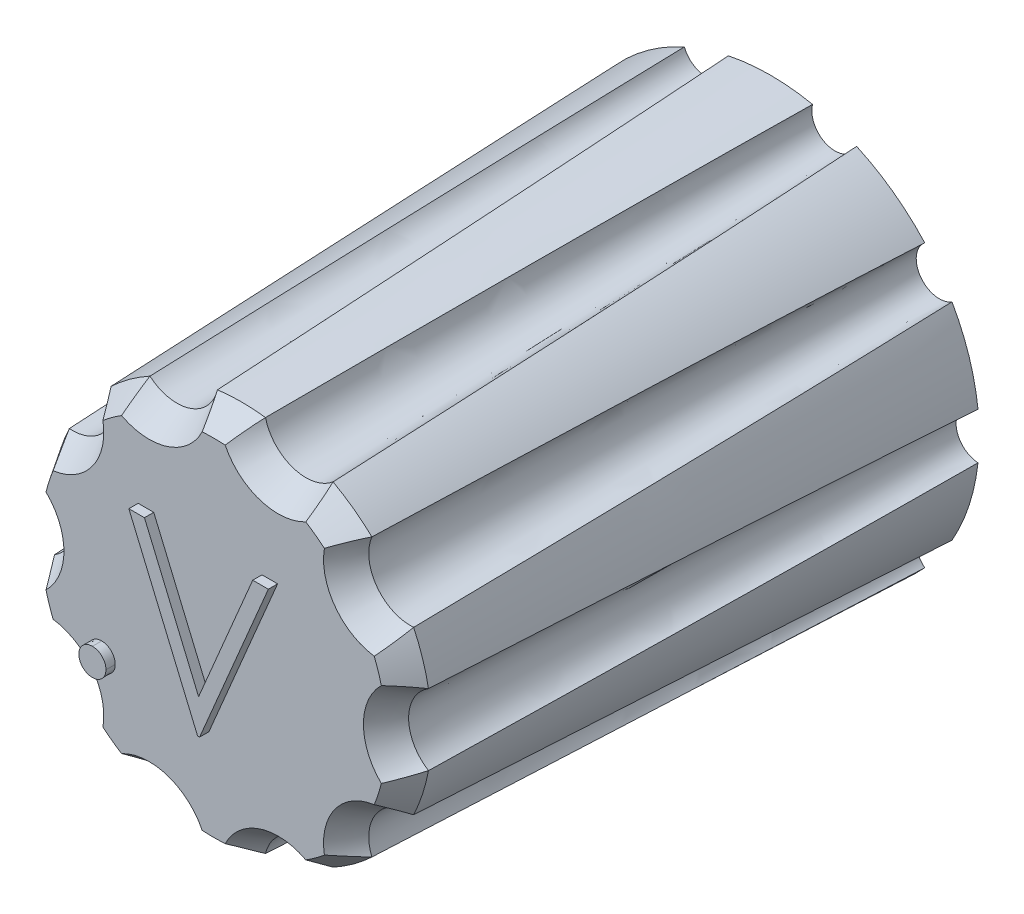
SolidWorks part; units mm, degrees
note: The reader was unsure of these and kept them because the rebuilt part matched: shared geometry of "Esquisse5<2>".
ref_plane "Plan de face" through (0, 0, 0) normal (0, 0, 1) x (1, 0, 0)
ref_plane "Plan de dessus" through (0, 0, 0) normal (0, 1, 0) x (1, 0, 0)
ref_plane "Plan de droite" through (0, 0, 0) normal (1, 0, 0) x (0, 0, -1)
sketch "Esquisse1" plane through (0, 0, 0) normal (0, 0, 1) x (1, 0, 0)
  line L0 (-13.0824, 0) -> (17.5938, 0) construction
  circle A0 centre (0, 0) radius 4.5
  circle A1 centre (-4.5, 0) radius 0.5
  circle A2 centre (-3.6406, 2.645) radius 0.5
  circle A3 centre (-1.3906, 4.2798) radius 0.5
  circle A4 centre (1.3906, 4.2798) radius 0.5
  circle A5 centre (3.6406, 2.645) radius 0.5
  circle A6 centre (4.5, 0) radius 0.5
  circle A7 centre (3.6406, -2.645) radius 0.5
  circle A8 centre (1.3906, -4.2798) radius 0.5
  circle A9 centre (-1.3906, -4.2798) radius 0.5
  circle A10 centre (-3.6406, -2.645) radius 0.5
  point P35 (0, 0)
  dimension "D1" = 9
  dimension "D2" = 1
  dimension "D3" = 10
extrude "Boss.-Extru.1" add sketch "Esquisse1" along normal blind 12 draft 2
chamfer "Chanfrein2" distance 0.6 angle 30 20 edges at (-3.8812, 1.2611, 12) (-2.8971, 2.1048, 12) (-2.3987, 3.3016, 12) (-1.1066, 3.4057, 12) (0, 4.081, 12) (1.1066, 3.4057, 12) (2.3987, 3.3016, 12) (2.8971, 2.1048, 12) (3.8812, 1.2611, 12) (3.581, 0, 12) (3.8812, -1.2611, 12) (2.8971, -2.1048, 12) (2.3987, -3.3016, 12) (1.1066, -3.4057, 12) (0, -4.081, 12) (-1.1066, -3.4057, 12) (-2.3987, -3.3016, 12) (-2.8971, -2.1048, 12) (-3.8812, -1.2611, 12) (-3.581, 0, 12)
sketch "Esquisse2" plane through (0, 0, 0) normal (0, 0, -1) x (-1, 0, 0)
  line L0 (2.6552, -1.6) -> (-2.6552, -1.6)
  circle A0 centre (0, 0) radius 3.1
  dimension "D1" = 6.2
  dimension "D2" = 1.6
extrude "Enlèv. mat.-Extru.1" cut sketch "Esquisse2" against normal blind 10 contours L0 A0
sketch "Esquisse4" plane through (0, 0, 0) normal (0, 0, -1) x (-1, 0, 0)
  line L0 (2.6552, -1.6) -> (-2.6552, -1.6) construction
  circle A0 centre (-2.6552, -1.6) radius 0.2
  circle A1 centre (2.5981, -1.6) radius 0.2
  dimension "D1" = 0.4
  dimension "D2" = 0.4
extrude "Enlèv. mat.-Extru.4" cut sketch "Esquisse4" against normal blind 10
sketch "Esquisse5" plane through (0, 0, 12) normal (0, 0, 1) x (1, 0, 0)
  line L0 (-3.1089, -1.8053) -> (3.1456, -1.8053) construction
  text T0 ".V"
extrude "Enlèv. mat.-Extru.5" cut sketch "Esquisse5" against normal blind 0.2
extrude "Boss.-Extru.2" add sketch "Esquisse5<2>" along normal blind 0.2 separate body
sketch "Esquisse5<2>" plane through (0, 0, 12) normal (0, 0, 1) x (1, 0, 0) same geometry as "Esquisse5"
chamfer "Chanfrein3" distance 0.2 angle 45 1 edges at (0.0286, -1.6, 0)
